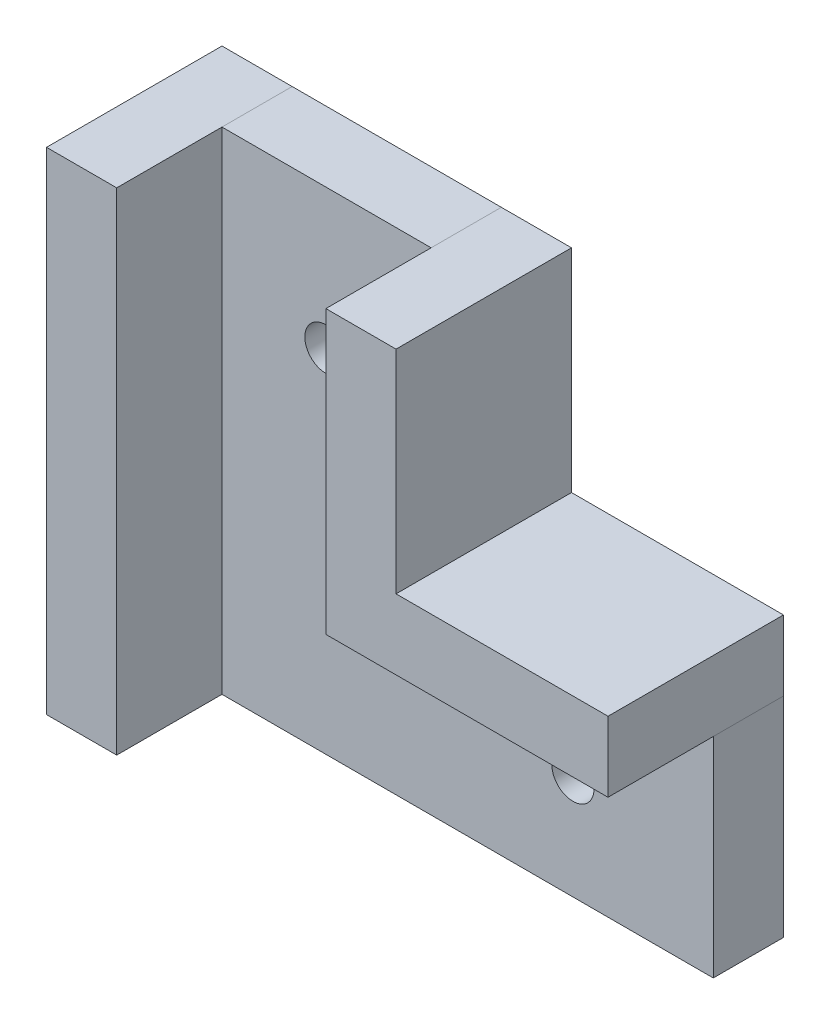
SolidWorks part; units mm, degrees
ref_plane "前视基准面" through (0, 0, 0) normal (0, 0, 1) x (1, 0, 0)
ref_plane "上视基准面" through (0, 0, 0) normal (0, 1, 0) x (1, 0, 0)
ref_plane "右视基准面" through (0, 0, 0) normal (1, 0, 0) x (0, 0, -1)
sketch "Sketch1" plane through (0, 0, 0) normal (0, 0, 1) x (1, 0, 0)
  line L0 (-7.5299, -25.8068) -> (27.4701, -25.8068)
  line L3 (-7.5299, 9.1932) -> (7.3701, 9.1932)
  line L4 (-7.5299, 9.1932) -> (-7.5299, -25.8068)
  line L6 (7.3701, 9.1932) -> (7.3701, -10.9068)
  line L7 (27.4701, -25.8068) -> (27.4701, -10.9068)
  line L8 (27.4701, -10.9068) -> (7.3701, -10.9068)
  dimension "D1" = 14.9
  dimension "D2" = 35
  dimension "D3" = 35
  dimension "D4" = 14.9
extrude "Boss-Extrude1" add sketch "Sketch1" along normal blind 5
sketch "Sketch2" plane through (0, 0, 0) normal (0, 0, -1) x (-1, 0, 0)
  line L0 (-7.3701, 9.1932) -> (-12.3701, 9.1932)
  line L1 (-12.3701, 9.1932) -> (-12.3701, -5.9068)
  line L2 (-12.3701, -5.9068) -> (-27.4701, -5.9068)
  line L3 (-27.4701, -10.9068) -> (-27.4701, -5.9068)
  line L4 (-27.4701, -10.9068) -> (-7.3701, -10.9068)
  line L5 (-7.3701, -10.9068) -> (-7.3701, 9.1932)
  dimension "D1" = 5
  dimension "D2" = 5
extrude "Boss-Extrude2" add sketch "Sketch2" against normal blind 12.5 separate body
sketch "Sketch3" plane through (0, 0, 0) normal (0, 0, -1) x (-1, 0, 0)
  line L0 (7.5299, 9.1932) -> (12.5299, 9.1932)
  line L1 (7.5299, -25.8068) -> (12.5299, -25.8068)
  line L2 (12.5299, -25.8068) -> (12.5299, 9.1932)
  line L3 (7.5299, -25.8068) -> (7.5299, 9.1932)
  dimension "D1" = 5
extrude "Boss-Extrude3" add sketch "Sketch3" against normal blind 12.5 separate body
sketch "Sketch4" plane through (0, 0, 0) normal (0, 0, -1) x (-1, 0, 0)
  line L0 (-27.4701, -10.9068) -> (-7.3701, -10.9068) construction
  line L1 (-27.4701, -25.8068) -> (-27.4701, -10.9068) construction
  line L2 (-7.3701, -10.9068) -> (-7.3701, 9.1932) construction
  line L3 (-7.3701, 9.1932) -> (7.5299, 9.1932) construction
  circle A0 centre (0.1299, -0.8068) radius 1.5
  circle A1 centre (-17.4701, -18.4068) radius 1.5
  dimension "D1" = 3
  dimension "D2" = 3
  dimension "D3" = 7.5
  dimension "D4" = 10
  dimension "D5" = 7.5
  dimension "D6" = 10
extrude "Cut-Extrude1" cut sketch "Sketch4" against normal through all
